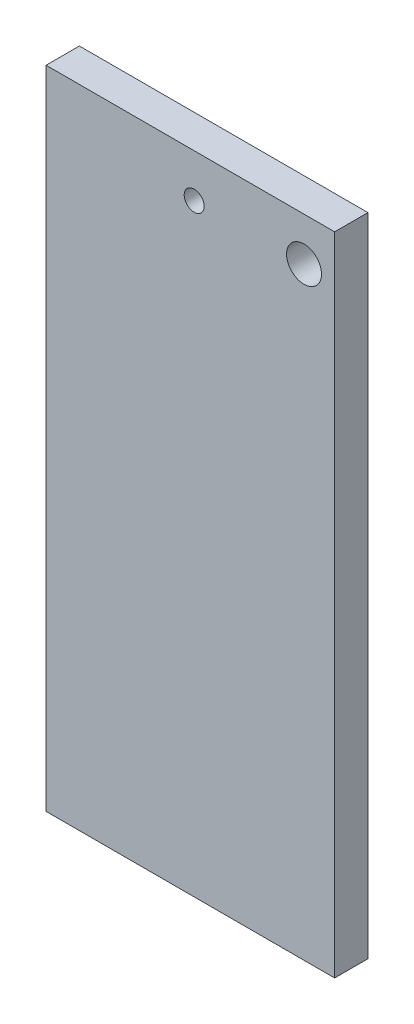
SolidWorks part; units mm, degrees
ref_plane "Front Plane" through (0, 0, 0) normal (0, 0, 1) x (1, 0, 0)
ref_plane "Top Plane" through (0, 0, 0) normal (0, 1, 0) x (1, 0, 0)
ref_plane "Right Plane" through (0, 0, 0) normal (1, 0, 0) x (0, 0, -1)
sketch "Sketch1" plane through (0, 0, 0) normal (0, 0, 1) x (1, 0, 0)
  line L0 (-13.2548, 13) -> (66, 13) construction
  line L1 (63.9411, 13) -> (-22.7426, 13)
  line L2 (63.9411, 13) -> (63.9411, -181.1389)
  line L3 (63.9411, -181.1389) -> (-22.7426, -181.1389)
  line L4 (-22.7426, 13) -> (-22.7426, -181.1389)
  circle A0 centre (21.75, 0) radius 3 construction
  circle A1 centre (54.75, 0) radius 5.25 construction
  circle A2 centre (21.75, 0) radius 3
  circle A3 centre (54.75, 0) radius 5.25
extrude "Boss-Extrude2" add sketch "Sketch1" along normal blind 10
